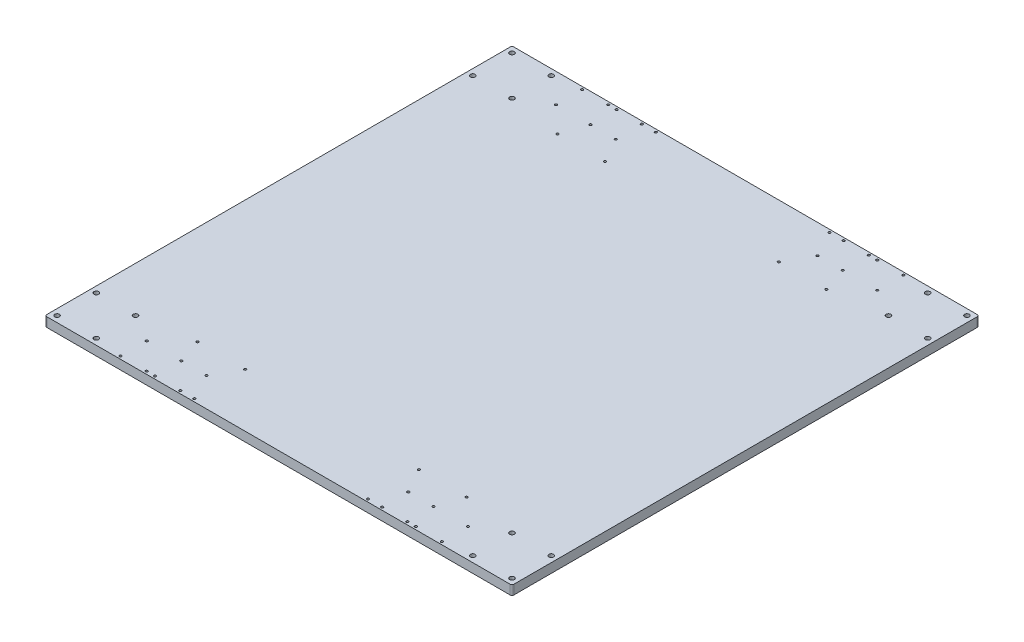
SolidWorks part; units mm, degrees
material "AISI 1045 Steel, cold drawn"
ref_plane "Front Plane" through (0, 0, 0) normal (0, 0, 1) x (1, 0, 0)
ref_plane "Top Plane" through (0, 0, 0) normal (0, 1, 0) x (1, 0, 0)
ref_plane "Right Plane" through (0, 0, 0) normal (1, 0, 0) x (0, 0, -1)
sketch "Sketch1" plane through (0, 0, 0) normal (0, 1, 0) x (1, 0, 0)
  line L1 (250, -250) -> (-250, -250)
  line L2 (250, -250) -> (250, 250)
  line L3 (250, 250) -> (-250, 250)
  line L4 (-250, -250) -> (-250, 250)
  line L5 (250, -250) -> (-250, 250) construction
  line L6 (250, 250) -> (-250, -250) construction
  point P0 (0, 0)
  dimension "D1" = 500
extrude "Boss-Extrude1" add sketch "Sketch1" along normal blind 10
sketch "Sketch2" plane through (0, 10, 0) normal (0, 1, 0) x (1, 0, 0)
  line L0 (250, -250) -> (250, 250) construction
  line L1 (172, -247) -> (108, -247)
  line L2 (172, -247) -> (172, -219)
  line L3 (172, -219) -> (108, -219)
  line L4 (108, -247) -> (108, -219)
  line L5 (-250, -250) -> (250, -250) construction
  line L6 (0, -1000) -> (0, 49000) construction
  line L7 (-108, -247) -> (-108, -219)
  line L8 (-172, -219) -> (-108, -219)
  line L9 (-172, -247) -> (-172, -219)
  line L10 (-172, -247) -> (-108, -247)
  line L11 (-1000, 0) -> (49000, 0) construction
  line L12 (-172, 247) -> (-108, 247)
  line L13 (-172, 247) -> (-172, 219)
  line L14 (-172, 219) -> (-108, 219)
  line L15 (-108, 247) -> (-108, 219)
  line L16 (108, 247) -> (108, 219)
  line L17 (172, 219) -> (108, 219)
  line L18 (172, 247) -> (172, 219)
  line L19 (172, 247) -> (108, 247)
  line L20 (-144, -192.6) -> (-93, -192.6)
  line L21 (144, -247) -> (93, -247)
  line L22 (144, -247) -> (144, -192.6)
  line L23 (144, -192.6) -> (93, -192.6)
  line L24 (93, -247) -> (93, -192.6)
  line L25 (-93, -247) -> (-93, -192.6)
  line L26 (-144, -247) -> (-93, -247)
  line L27 (-144, -247) -> (-144, -192.6)
  line L28 (144, 192.6) -> (93, 192.6)
  line L29 (93, 247) -> (93, 192.6)
  line L30 (144, 247) -> (93, 247)
  line L31 (144, 247) -> (144, 192.6)
  line L32 (-144, 247) -> (-144, 192.6)
  line L33 (-144, 247) -> (-93, 247)
  line L34 (-93, 247) -> (-93, 192.6)
  line L35 (-144, 192.6) -> (-93, 192.6)
  point P41 (135, -219)
  point P42 (135, -247)
  point P43 (0, 0)
  point P44 (0, 0)
  point P45 (-135, -247)
  point P46 (-135, -219)
  point P47 (0, 0)
  point P48 (135, 247)
  point P49 (135, 219)
  point P50 (-135, 247)
  point P51 (-135, 219)
  dimension "D1" = 78
  dimension "D2" = 64
  dimension "D3" = 28
  dimension "D4" = 3
  dimension "D5" = 28
  dimension "D6" = 51
  dimension "D7" = 54.4
  dimension "D8" = 37
hole_wizard "Tap Drill for M3x0.5 Tap1" positions "Sketch3" profile "Sketch4" hole size "M3x0.5" standard "ANSI Metric" end condition through all
sketch "Sketch3" plane through (0, 10, 0) normal (0, 1, 0) x (1, 0, 0)
  point P0 (172, -219)
  point P3 (172, -247)
  point P6 (108, -247)
  point P9 (108, -219)
  point P12 (-108, -219)
  point P15 (-172, -219)
  point P18 (-172, -247)
  point P21 (-108, -247)
  point P24 (-108, 219)
  point P27 (-108, 247)
  point P30 (-172, 247)
  point P33 (-172, 219)
  point P36 (108, 247)
  point P39 (172, 247)
  point P42 (172, 219)
  point P45 (108, 219)
  point P48 (-144, 247)
  point P51 (-93, 247)
  point P54 (-93, 192.6)
  point P56 (-144, 192.6)
  point P62 (93, 247)
  point P65 (144, 247)
  point P68 (144, 192.6)
  point P71 (93, 192.6)
  point P74 (93, -192.6)
  point P77 (144, -192.6)
  point P80 (144, -247)
  point P83 (93, -247)
  point P86 (-144, -192.6)
  point P89 (-93, -192.6)
  point P92 (-93, -247)
  point P95 (-144, -247)
  point P98 (-135, -219)
  point P101 (-135, -247)
  point P104 (135, -219)
  point P107 (135, -247)
  point P110 (135, 219)
  point P113 (135, 247)
  point P116 (-135, 219)
  point P119 (-135, 247)
sketch "Sketch4" plane through (172, 10, 219) normal (1, 0, 0) x (0, 0, 1)
  line L0 (0, 0) -> (0, 10)
  line L1 (0, 10) -> (1.25, 10)
  line L2 (1.25, 10) -> (1.25, 0)
  line L5 (1.25, 0) -> (0, 0)
  line L11 (0, -6.35) -> (0, 107.95) construction
  dimension "Thru Hole Dia." = 2.5
  dimension "Thru Hole Depth" = 10
hole_wizard "Tap Drill for M6x1.0 Tap1" positions "Sketch5" profile "Sketch6" hole size "M6x1.0" standard "ANSI Metric" end condition through all
sketch "Sketch5" plane through (0, 10, 0) normal (0, 1, 0) x (1, 0, 0)
  line L1 (243.5, -243.5) -> (201.5, -243.5)
  line L2 (243.5, -243.5) -> (243.5, -201.5)
  line L3 (243.5, -201.5) -> (201.5, -201.5)
  line L4 (201.5, -243.5) -> (201.5, -201.5)
  line L5 (201.5, -243.5) -> (243.5, -201.5) construction
  line L7 (250, -250) -> (250, 250) construction
  line L8 (-250, -250) -> (250, -250) construction
  circle A0 centre (222.5, -222.5) radius 27.5
  point P1 (243.5, -243.5)
  point P2 (201.5, -201.5)
  point P39 (243.5, -201.5)
  point P40 (201.5, -243.5)
  dimension "D3" = 55
  dimension "D1" = 42
  dimension "D2" = 42
sketch "Sketch6" plane through (243.5, 10, 243.5) normal (1, 0, 0) x (0, 0, 1)
  line L0 (0, 0) -> (0, 10)
  line L1 (0, 10) -> (2.5, 10)
  line L2 (2.5, 10) -> (2.5, 0)
  line L5 (2.5, 0) -> (0, 0)
  line L11 (0, -6.35) -> (0, 107.95) construction
  dimension "Thru Hole Dia." = 5
  dimension "Thru Hole Depth" = 10
ref_axis "Axis1" through (0, 10.5, 0) along (0, -1, 0)
pattern_circular "CirPattern1" count 4 over 360 about axis through (0, 10.5, 0) along (0, -1, 0) of "Tap Drill for M6x1.0 Tap1"
fillet "Fillet1" radius 2 4 edges at (250, 5, -250) (250, 5, 250) (-250, 5, 250) (-250, 5, -250)
